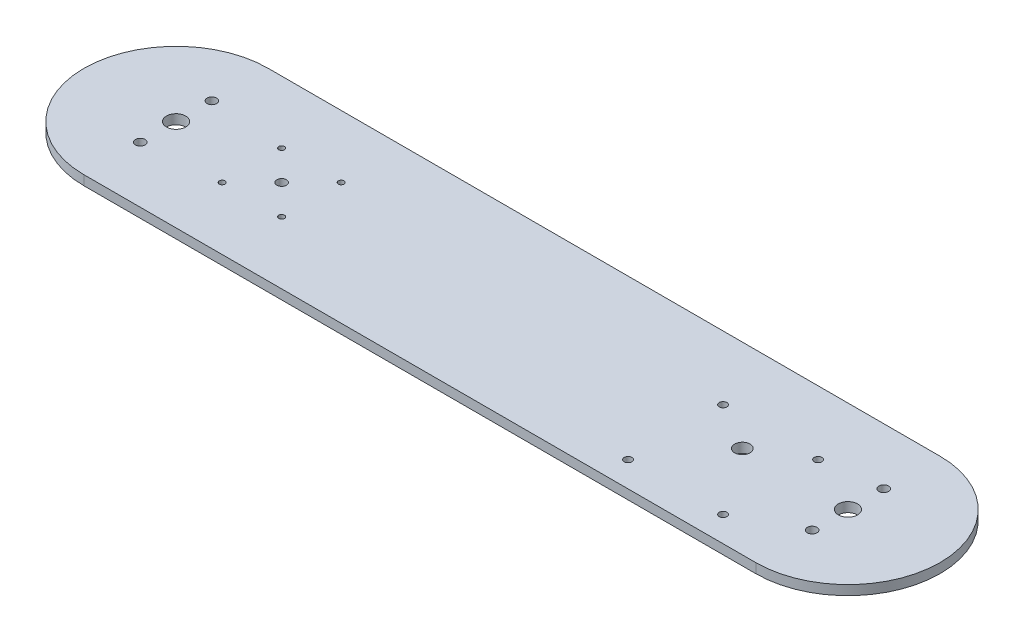
SolidWorks part; units mm, degrees
material "6061-T6 (SS)"
ref_plane "Front Plane" through (0, 0, 0) normal (0, 0, 1) x (1, 0, 0)
ref_plane "Top Plane" through (0, 0, 0) normal (0, 1, 0) x (1, 0, 0)
ref_plane "Right Plane" through (0, 0, 0) normal (1, 0, 0) x (0, 0, -1)
sketch "Sketch1" plane through (0, 0, 0) normal (0, 1, 0) x (1, 0, 0)
  line L0 (-175, 48) -> (175, 48)
  line L1 (0, 48) -> (0, -48) construction
  line L2 (175, -48) -> (-175, -48)
  arc A0 (-175, 48) -> (-175, -48) centre (-175, 0) ccw
  arc A1 (175, -48) -> (175, 48) centre (175, 0) ccw
  point P8 (0, 0)
  dimension "D1" = 96
  dimension "D2" = 350
extrude "Boss-Extrude1" add sketch "Sketch1" along normal blind 5
sketch "Sketch2" plane through (0, 0, 0) normal (0, -1, 0) x (1, 0, 0)
  line L1 (0, 48) -> (0, -48) construction
  line L2 (-175, 48) -> (175, 48) construction
  line L3 (175, -48) -> (-175, -48) construction
  line L4 (-175, 0) -> (-120, 0) construction
  line L5 (-135.5, 15.5) -> (-104.5, 15.5) construction
  line L10 (-135.5, 15.5) -> (-135.5, -15.5) construction
  line L11 (-135.5, -15.5) -> (-104.5, -15.5) construction
  line L13 (-104.5, 15.5) -> (-104.5, -15.5) construction
  line L14 (95.25, 34.8) -> (144.75, 34.8) construction
  line L15 (95.25, 34.8) -> (95.25, -14.7) construction
  line L16 (95.25, -14.7) -> (144.75, -14.7) construction
  line L17 (144.75, 34.8) -> (144.75, -14.7) construction
  circle A0 centre (175, 0) radius 5
  circle A1 centre (175, 18.65) radius 2.5
  circle A2 centre (175, -18.65) radius 2.5
  circle A5 centre (-175, -18.65) radius 2.5
  circle A6 centre (-175, 18.65) radius 2.5
  circle A7 centre (-175, 0) radius 5
  circle A12 centre (120, 0) radius 4
  circle A14 centre (95.25, -14.7) radius 2
  circle A15 centre (144.75, -14.7) radius 2
  circle A16 centre (144.75, 34.8) radius 2
  circle A17 centre (95.25, 34.8) radius 2
  circle A18 centre (-135.5, -15.5) radius 1.5
  circle A19 centre (-135.5, 15.5) radius 1.5
  circle A20 centre (-104.5, 15.5) radius 1.5
  circle A21 centre (-104.5, -15.5) radius 1.5
  circle A22 centre (-120, 0) radius 2.5
  point P32 (0, 0)
  point P33 (0, 0)
  dimension "D1" = 10
  dimension "D2" = 5
  dimension "D6" = 4
  dimension "D10" = 3
  dimension "D14" = 4
  dimension "D9" = 5
  dimension "D3" = 18.65
  dimension "D4" = 37.3
  dimension "D5" = 55
  dimension "D7" = 14.7
  dimension "D8" = 31
  dimension "D11" = 49.5
  dimension "D12" = 15.5
  dimension "D13" = 24.75
  dimension "D15" = 15.5
extrude "Cut-Extrude1" cut sketch "Sketch2" against normal blind 10 contours A1 | A0 | A12 | A17 | A15 | A14 | A7 | A21 | A19 | A20 | A18 | A22 | A2 | A16 | A5 | A6 region at (175, 0, 0) region at (175, 0, 18.65) region at (-175, 0, 0) region at (120, 0, 0) region at (95.25, 0, -14.7) region at (144.75, 0, -14.7) region at (95.25, 0, 34.8) region at (-135.5, 0, -15.5) region at (-135.5, 0, 15.5) region at (-104.5, 0, 15.5) region at (-104.5, 0, -15.5) region at (-120, 0, 0)
